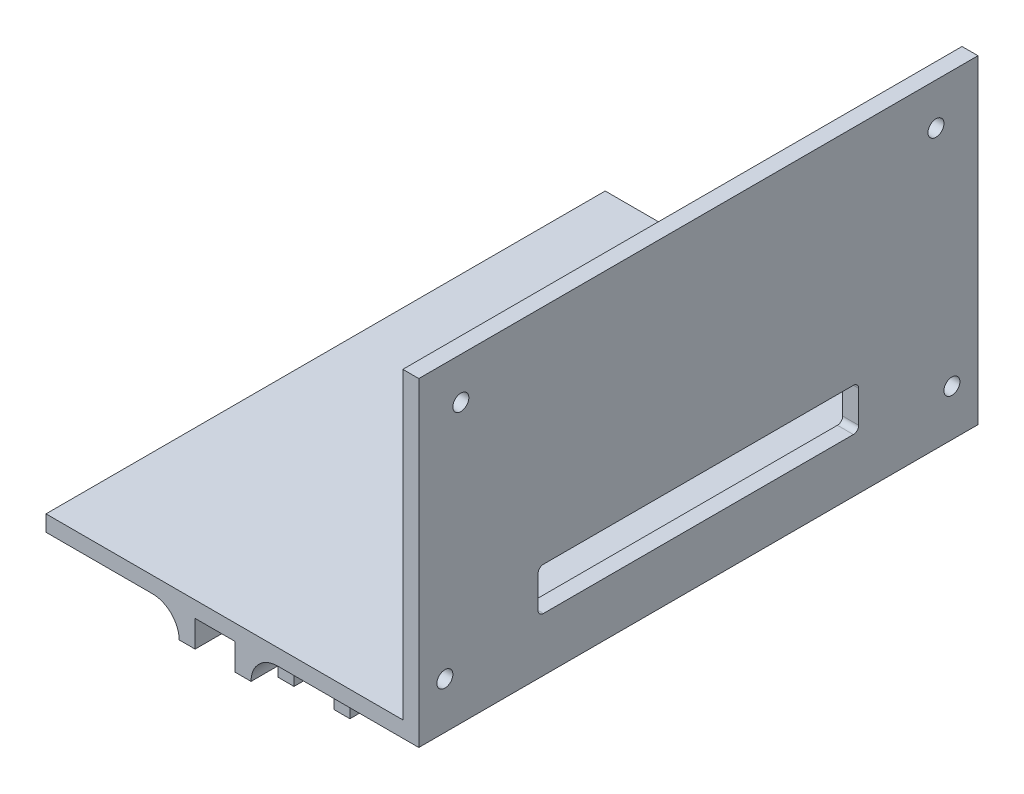
SolidWorks part; units mm, degrees
ref_plane "Front Plane" through (0, 0, 0) normal (0, 0, 1) x (1, 0, 0)
ref_plane "Top Plane" through (0, 0, 0) normal (0, 1, 0) x (1, 0, 0)
ref_plane "Right Plane" through (0, 0, 0) normal (1, 0, 0) x (0, 0, -1)
sketch "Sketch2" plane through (0, 0, 0) normal (0, 0, 1) x (1, 0, 0)
  line L0 (18.505, 30) -> (45, 30)
  line L1 (0, 0) -> (3, 0)
  line L2 (0, 0) -> (0, 25)
  line L4 (3, 0) -> (3, 30)
  line L5 (0, 33) -> (42, 33)
  line L7 (3, 30) -> (10.505, 30)
  line L10 (45, 30) -> (45, 90)
  line L11 (45, 90) -> (42, 90)
  line L12 (42, 33) -> (42, 90)
  line L14 (10.505, 30) -> (10.505, 0)
  line L15 (10.505, 0) -> (13.505, 0)
  line L16 (13.505, 25) -> (13.505, 0)
  line L18 (0, 33) -> (-25, 33)
  line L20 (-5, 30) -> (-25, 30)
  line L21 (-25, 33) -> (-25, 30)
  arc A0 (18.505, 30) -> (13.505, 25) centre (18.505, 25) ccw
  arc A1 (0, 25) -> (-5, 30) centre (-5, 25) ccw
  point P20 (0, 30)
  dimension "D10" = 5
  dimension "D1" = 7.505
  dimension "D2" = 3
  dimension "D3" = 3
  dimension "D4" = 3
  dimension "D5" = 3
  dimension "D6" = 60
  dimension "D7" = 45
  dimension "D8" = 3
  dimension "D9" = 25
  dimension "D11" = 25
  dimension "D12" = 25
extrude "Boss-Extrude1" add sketch "Sketch2" along normal blind 105
sketch "Sketch3" plane through (0, 0, 0) normal (-1, 0, 0) x (0, 0, 1)
  line L0 (52.5, 0) -> (52.5, 25) construction
  line L1 (105, 0) -> (0, 0) construction
  line L2 (105, 25) -> (0, 25) construction
  line L3 (105, 30) -> (0, 30) construction
  circle A0 centre (26.25, 20.25) radius 2.75
  circle A1 centre (78.75, 20.25) radius 2.75
  dimension "D1" = 5.5
  dimension "D2" = 26.25
  dimension "D3" = 9.75
extrude "Cut-Extrude1" cut sketch "Sketch3" against normal through all
sketch "Sketch5" plane through (42, 0, 0) normal (-1, 0, 0) x (0, 0, 1)
  line L0 (52.5, 33) -> (52.5, 90) construction
  line L1 (105, 33) -> (0, 33) construction
  line L2 (105, 90) -> (0, 90) construction
  circle A4 centre (4.9, 38.71) radius 1.5
  circle A5 centre (100.1, 38.71) radius 1.5
  circle A6 centre (7.8929, 82.1871) radius 1.5
  circle A7 centre (97.1071, 82.1871) radius 1.5
  dimension "D1" = 3
  dimension "D2" = 95.2
  dimension "D3" = 5.71
  dimension "D4" = 3
  dimension "D5" = 43.58
extrude "Cut-Extrude2" cut sketch "Sketch5" against normal through all
sketch "Sketch7" plane through (0, 0, 0) normal (0, 0, -1) x (-1, 0, 0)
  line L1 (-18.505, 30) -> (6.3663, 30)
  line L2 (-18.505, 30) -> (-18.505, 0)
  line L3 (-18.505, 0) -> (6.3663, 0)
  line L4 (6.3663, 30) -> (6.3663, 0)
extrude "Cut-Extrude5" cut sketch "Sketch7" against normal blind 19.5 contours L2 L3 L4 L1
fillet "Fillet1" radius 19.5 2 edges at (-1, 30, 19.5) (14.505, 30, 19.5)
sketch "Sketch9" plane through (42, 0, 0) normal (-1, 0, 0) x (0, 0, 1)
  line L0 (105, 90) -> (105, 33) construction
  line L1 (23.4, 48.1) -> (81.6, 48.1)
  line L2 (22.4, 47.1) -> (22.4, 41.1)
  line L3 (23.4, 40.1) -> (81.6, 40.1)
  line L4 (82.6, 47.1) -> (82.6, 41.1)
  line L11 (105, 33) -> (0, 33) construction
  line L27 (52.5, 48.1) -> (52.5, 33) construction
  line L42 (105, 33) -> (0, 33) construction
  line L43 (0, 90) -> (0, 33) construction
  arc A3 (81.6, 40.1) -> (82.6, 41.1) centre (81.6, 41.1) ccw
  arc A4 (81.6, 48.1) -> (82.6, 47.1) centre (81.6, 47.1) cw
  arc A5 (23.4, 48.1) -> (22.4, 47.1) centre (23.4, 47.1) ccw
  arc A6 (22.4, 41.1) -> (23.4, 40.1) centre (23.4, 41.1) ccw
  point P24 (91.09, 86.0779)
  point P33 (22.4, 40.1)
  point P36 (13.91, 86.0779)
  point P39 (52.5, 61.8071)
  point P42 (90.6683, 83.3459)
  point P46 (81.5469, 28.6593)
  point P49 (52.5, 45.3004)
  point P58 (87.6683, 77.9089)
  dimension "D3" = 22.4
  dimension "D4" = 1
  dimension "D1" = 22.4
  dimension "D2" = 7.1
  dimension "D5" = 8
extrude "Cut-Extrude6" cut sketch "Sketch9" against normal through all
sketch "Sketch10" plane through (0, 0, 0) normal (-1, 0, 0) x (0, 0, 1)
  line L0 (105, 0) -> (19.5, 0) construction
  line L1 (36.005, 0) -> (70.6685, 0)
  line L2 (36.005, 9.6496) -> (36.005, 25)
  line L3 (36.005, 25) -> (70.6685, 25)
  line L4 (70.6685, 9.6496) -> (70.6685, 25)
  line L5 (105, 25) -> (13.0384, 25) construction
  line L6 (105, 25) -> (105, 0) construction
  line L7 (86.4381, 25) -> (105, 25)
  line L8 (86.4381, 25) -> (86.4381, 9.6496)
  line L9 (86.4381, 0) -> (105, 0)
  line L10 (105, 25) -> (105, 0)
  line L11 (19.5, 10.5) -> (19.5, 0) construction
  line L12 (19.5, 9.6496) -> (36.005, 9.6496)
  line L13 (19.5, 9.6496) -> (19.5, 0)
  line L14 (19.5, 0) -> (105, 0)
  line L15 (105, 9.6496) -> (105, 0)
  line L16 (70.6685, 9.6496) -> (86.4381, 9.6496)
  line M7 (105, 25) -> (13.0384, 25)
  line M9 (19.5, 10.5) -> (19.5, 0)
  line M10 (19.5, 0) -> (105, 0)
  line M11 (105, 0) -> (105, 25)
extrude "Cut-Extrude8" cut sketch "Sketch10" against normal through all contours L16 L4 L2 L12 L10 L8 M7 M9 M10 M11 region at (0, 11.0443, 65.1693)
fillet "Fillet2" radius 10 6 edges at (12.005, 25, 70.6685) (1.5, 25, 70.6685) (12.005, 25, 86.4381) (1.5, 25, 86.4381) (12.005, 25, 36.005) (1.5, 25, 36.005)
